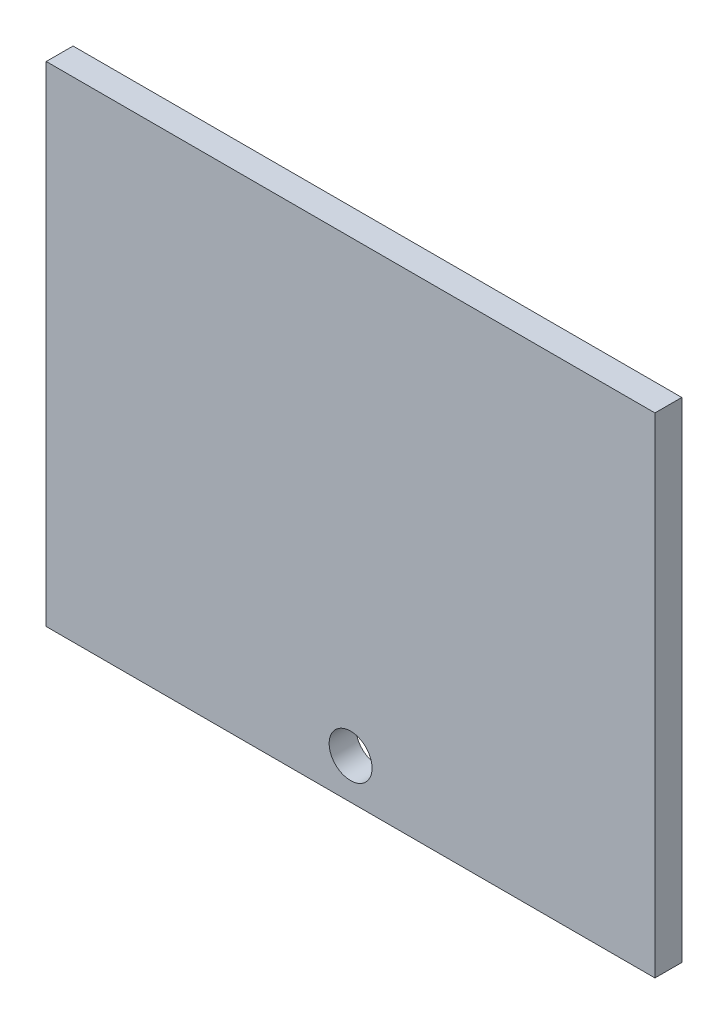
SolidWorks part; units mm, degrees
ref_plane "前视基准面" through (0, 0, 0) normal (0, 0, 1) x (1, 0, 0)
ref_plane "上视基准面" through (0, 0, 0) normal (0, 1, 0) x (1, 0, 0)
ref_plane "右视基准面" through (0, 0, 0) normal (1, 0, 0) x (0, 0, -1)
sketch "草图1" plane through (0, 0, 0) normal (0, 0, 1) x (1, 0, 0)
  line L1 (-72.441, 43.6117) -> (-27.041, 43.6117)
  line L2 (-72.441, 43.6117) -> (-72.441, 7.1117)
  line L3 (-72.441, 7.1117) -> (-27.041, 7.1117)
  line L4 (-27.041, 43.6117) -> (-27.041, 7.1117)
  dimension "D1" = 36.5
  dimension "D2" = 45.4
extrude "凸台-拉伸1" add sketch "草图1" along normal blind 2
sketch "草图10" plane through (0, 0, 0) normal (0, 0, -1) x (-1, 0, 0)
  line L0 (49.741, 43.6117) -> (49.741, 7.1117) construction
  line L1 (27.041, 43.6117) -> (72.441, 43.6117) construction
  line L2 (72.441, 7.1117) -> (27.041, 7.1117) construction
  circle A0 centre (39.741, 20.1117) radius 2.95
  circle A1 centre (59.741, 20.1117) radius 2.95
  circle A2 centre (49.741, 10.1117) radius 1.6
  dimension "D1" = 5.9
  dimension "D2" = 10
  dimension "D3" = 23.5
  dimension "D4" = 3.2
  dimension "D5" = 3
extrude "切除-拉伸9" cut sketch "草图10" against normal through all contours A2 L0 | L0 A2 region at (-50.4201, 10.1117, 0) region at (-49.062, 10.1117, 0)
extrude "凸台-拉伸3" add sketch "草图10<3>" along normal blind 1.7 contours A1 | A0 region at (-59.741, 20.1117, 0)
sketch "草图10<3>" plane through (0, 0, 0) normal (0, 0, -1) x (-1, 0, 0) same geometry as "草图10"
